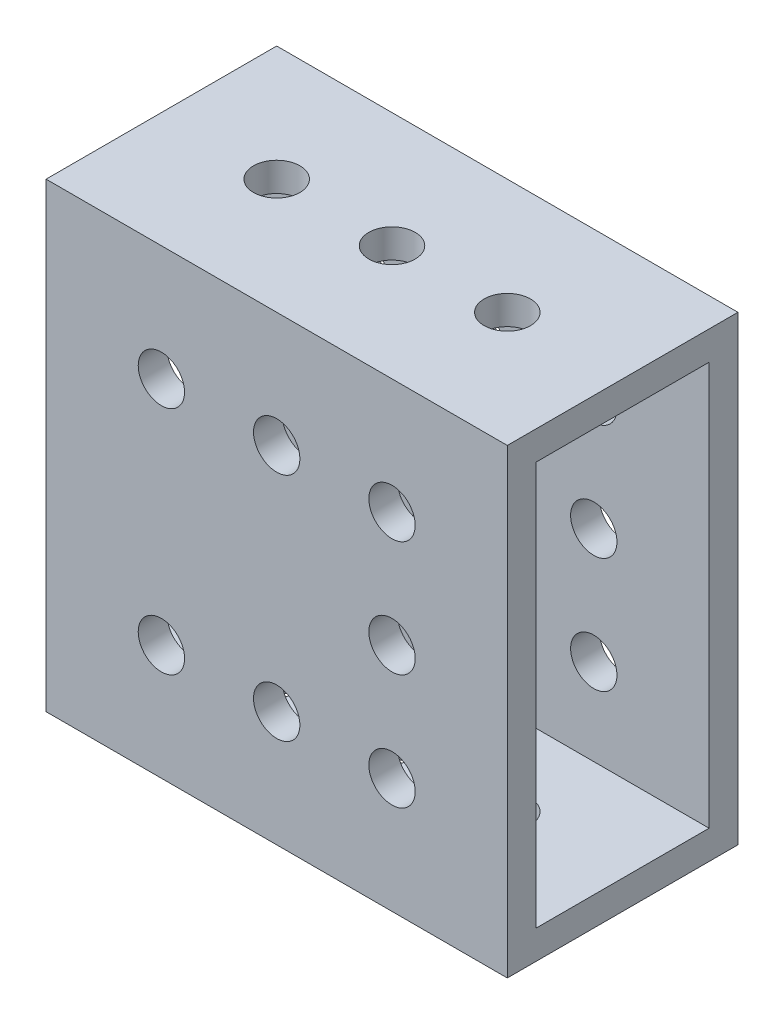
SolidWorks part; units mm, degrees
material "6061-T6 (SS)"
ref_plane "Front Plane" through (0, 0, 0) normal (0, 0, 1) x (1, 0, 0)
ref_plane "Top Plane" through (0, 0, 0) normal (0, 1, 0) x (1, 0, 0)
ref_plane "Right Plane" through (0, 0, 0) normal (1, 0, 0) x (0, 0, -1)
sketch "Sketch1" plane through (0, 0, 0) normal (0, 0, 1) x (1, 0, 0)
  line L1 (0, 0) -> (50.8, 0)
  line L2 (0, 0) -> (0, 50.8)
  line L3 (0, 50.8) -> (50.8, 50.8)
  line L4 (50.8, 0) -> (50.8, 50.8)
  dimension "D1" = 50.8
  dimension "D2" = 50.8
extrude "Boss-Extrude1" add sketch "Sketch1" along normal blind 25.4
sketch "Sketch2" plane through (50.8, 0, 0) normal (1, 0, 0) x (0, 0, -1)
  line L0 (-25.4, 0) -> (0, 0) construction
  line L1 (0, 0) -> (0, 50.8) construction
  line L2 (-25.4, 50.8) -> (0, 50.8) construction
  line L3 (-22.225, 3.175) -> (-3.175, 3.175)
  line L4 (-22.225, 3.175) -> (-22.225, 47.625)
  line L5 (-22.225, 47.625) -> (-3.175, 47.625)
  line L6 (-3.175, 3.175) -> (-3.175, 47.625)
  line L8 (-25.4, 0) -> (-25.4, 50.8) construction
  dimension "D1" = 3.175
  dimension "D2" = 3.175
  dimension "D3" = 3.175
  dimension "D4" = 3.175
extrude "Cut-Extrude1" cut sketch "Sketch2" against normal through all
sketch "Sketch3" plane through (0, 50.8, 0) normal (0, 1, 0) x (1, 0, 0)
  line L0 (50.8, 0) -> (0, 0) construction
  line L1 (0, -25.4) -> (0, 0) construction
  line L2 (50.8, -25.4) -> (0, -25.4) construction
  circle A0 centre (12.7, -12.7) radius 2.5527
  circle A1 centre (25.4, -12.7) radius 2.5527
  circle A2 centre (38.1, -12.7) radius 2.5527
  dimension "D1" = 12.7
  dimension "D2" = 12.7
  dimension "D3" = 12.7
  dimension "D4" = 12.7
  dimension "D5" = 5.1054
  dimension "D6" = 12.7
  dimension "D7" = 12.7
sketch "Sketch4" plane through (0, 0, 0) normal (0, 0, -1) x (-1, 0, 0)
  line L0 (-50.8, 0) -> (-50.8, 50.8) construction
  line L1 (-50.8, 50.8) -> (0, 50.8) construction
  line L2 (-22.8473, 50.8) -> (-27.9527, 50.8) construction
  line L4 (0, 50.8) -> (0, 0) construction
  circle A0 centre (-38.1, 38.1) radius 2.5527
  circle A1 centre (-25.4, 38.1) radius 2.5527
  circle A2 centre (-12.7, 38.1) radius 2.5527
  circle A3 centre (-38.1, 12.7) radius 2.5527
  circle A4 centre (-25.4, 12.7) radius 2.5527
  circle A5 centre (-12.7, 12.7) radius 2.5527
  circle A6 centre (-38.1, 25.4) radius 2.5527
  dimension "D1" = 12.7
  dimension "D2" = 12.7
  dimension "D3" = 12.7
  dimension "D4" = 5.1054
  dimension "D5" = 12.7
  dimension "D6" = 12.7
  dimension "D7" = 12.7
  dimension "D8" = 5.1054
  dimension "D9" = 12.7
  dimension "D10" = 25.4
  dimension "D11" = 3
  dimension "D12" = 12.7
  dimension "D13" = 25.4
  dimension "D14" = 5.1054
  dimension "D15" = 12.7
extrude "Cut-Extrude2" cut sketch "Sketch3" against normal through all
extrude "Cut-Extrude3" cut sketch "Sketch4" against normal through all
